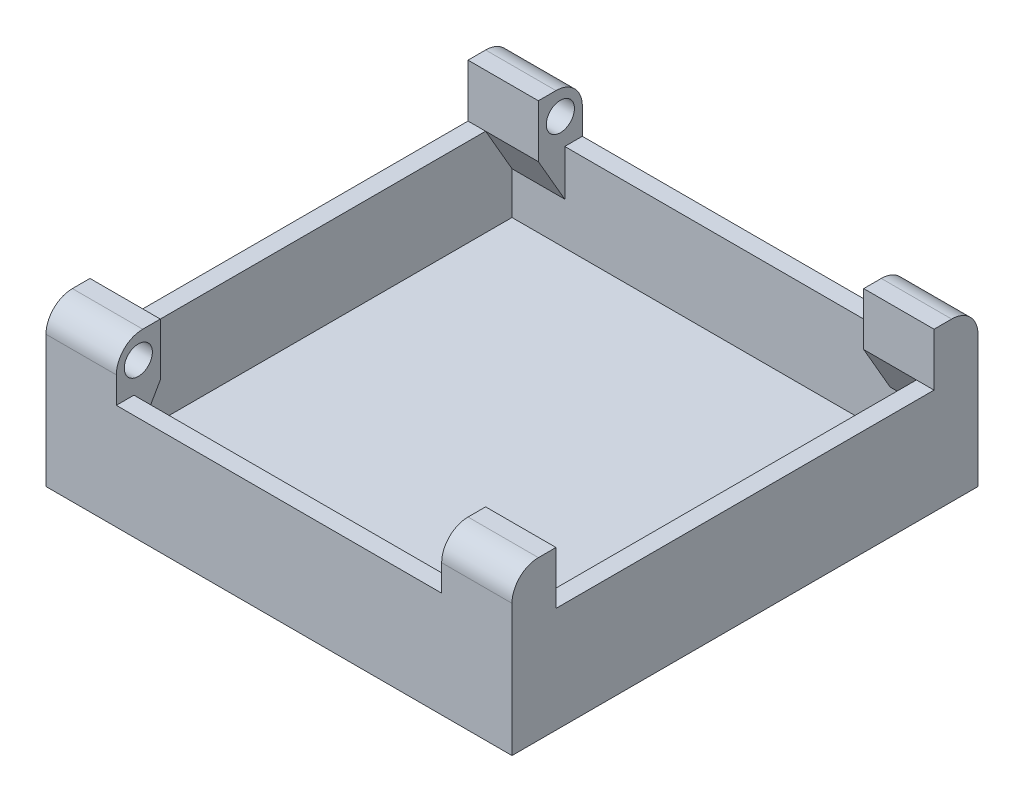
SolidWorks part; units mm, degrees
ref_plane "Front Plane" through (0, 0, 0) normal (0, 0, 1) x (1, 0, 0)
ref_plane "Top Plane" through (0, 0, 0) normal (0, 1, 0) x (1, 0, 0)
ref_plane "Right Plane" through (0, 0, 0) normal (1, 0, 0) x (0, 0, -1)
sketch "Sketch1" plane through (0, 0, 0) normal (0, 1, 0) x (1, 0, 0)
  line L1 (-26.5, -26.5) -> (26.5, -26.5)
  line L2 (-26.5, -26.5) -> (-26.5, 26.5)
  line L3 (-26.5, 26.5) -> (26.5, 26.5)
  line L4 (26.5, -26.5) -> (26.5, 26.5)
  line L5 (-26.5, -26.5) -> (26.5, 26.5) construction
  line L6 (-26.5, 26.5) -> (26.5, -26.5) construction
  line L10 (-24.5, 24.5) -> (24.5, 24.5)
  line L11 (24.5, -24.5) -> (24.5, 24.5)
  line L12 (-24.5, -24.5) -> (24.5, -24.5)
  line L13 (-24.5, -24.5) -> (-24.5, 24.5)
  point P0 (0, 0)
  dimension "D1" = 53
  dimension "D2" = 53
  dimension "D3" = 2
extrude "Boss-Extrude1" add sketch "Sketch1" along normal blind 10
sketch "Sketch2" plane through (0, 0, 0) normal (0, -1, 0) x (1, 0, 0)
  line L1 (-26.5, -26.5) -> (26.5, -26.5)
  line L2 (-26.5, -26.5) -> (-26.5, 26.5)
  line L3 (-26.5, 26.5) -> (26.5, 26.5)
  line L4 (26.5, -26.5) -> (26.5, 26.5)
extrude "Boss-Extrude2" add sketch "Sketch2" along normal blind 2
sketch "Sketch3" plane through (0, 10, 0) normal (0, 1, 0) x (1, 0, 0)
  line L0 (0, -40.6881) -> (0, 40.6881) construction
  line L1 (-26.5, -26.5) -> (-18.5, -26.5)
  line L2 (-26.5, -26.5) -> (-26.5, -21.5)
  line L3 (-26.5, -21.5) -> (-18.5, -21.5)
  line L4 (-18.5, -26.5) -> (-18.5, -21.5)
  line L5 (26.5, -21.5) -> (18.5, -21.5)
  line L6 (18.5, -26.5) -> (18.5, -21.5)
  line L7 (26.5, -26.5) -> (18.5, -26.5)
  line L8 (26.5, -26.5) -> (26.5, -21.5)
  line L9 (-39.9594, 0) -> (39.9594, 0) construction
  line L10 (26.5, 26.5) -> (26.5, 21.5)
  line L11 (26.5, 26.5) -> (18.5, 26.5)
  line L12 (18.5, 26.5) -> (18.5, 21.5)
  line L13 (26.5, 21.5) -> (18.5, 21.5)
  line L14 (-26.5, 21.5) -> (-18.5, 21.5)
  line L15 (-18.5, 26.5) -> (-18.5, 21.5)
  line L16 (-26.5, 26.5) -> (-18.5, 26.5)
  line L17 (-26.5, 26.5) -> (-26.5, 21.5)
  dimension "D1" = 5
  dimension "D2" = 8
extrude "Boss-Extrude3" add sketch "Sketch3" along normal blind 6
chamfer "Chamfer3" distance 3 angle 60 4 edges at (-21.5, 10, -24.5) (-21.5, 10, 24.5) (21.5, 10, 24.5) (21.5, 10, -24.5) first distance on face at (-21.5, 10, -23) first distance on face at (-21.5, 10, 23) first distance on face at (21.5, 10, 23) first distance on face at (21.5, 10, -23)
sketch "Sketch4" plane through (0, 0, 0) normal (1, 0, 0) x (0, 0, -1)
  line L0 (-26.5, 16) -> (-21.5, 16) construction
  line L5 (-21.5, 16) -> (-21.5, 10) construction
  line L6 (-21.5, 10) -> (-26.5, 10) construction
  line L7 (-26.5, 10) -> (-26.5, 16) construction
  line L8 (-24, 13.2) -> (-24, 10) construction
  line L9 (0, 39.9594) -> (0, -39.9594) construction
  circle A0 centre (-24, 13.2) radius 1.6
  circle A1 centre (24, 13.2) radius 1.6
  dimension "D1" = 3.2
  dimension "D2" = 3.2
extrude "Cut-Extrude1" cut sketch "Sketch4" against normal blind 22 and the other way blind 22
fillet "Fillet3" radius 3 4 edges at (22.5, 16, 26.5) (-22.5, 16, 26.5) (-22.5, 16, -26.5) (22.5, 16, -26.5)
